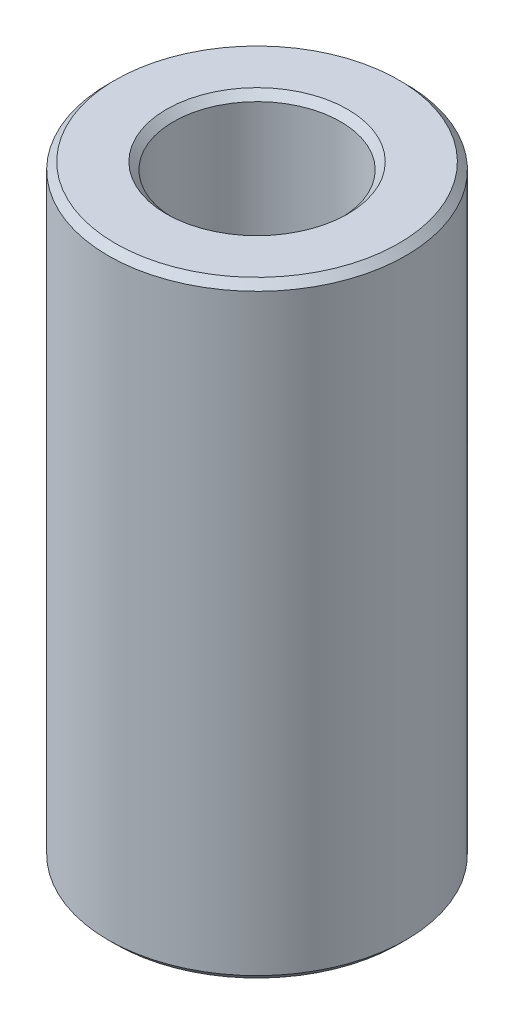
SolidWorks part; units mm, degrees
ref_plane "Front Plane" through (0, 0, 0) normal (0, 0, 1) x (1, 0, 0)
ref_plane "Top Plane" through (0, 0, 0) normal (0, 1, 0) x (1, 0, 0)
ref_plane "Right Plane" through (0, 0, 0) normal (1, 0, 0) x (0, 0, -1)
sketch "Sketch1" plane through (0, 0, 0) normal (0, 1, 0) x (1, 0, 0)
  circle A0 centre (0, 0) radius 40
  dimension "SLEEVE_OD" = 80
extrude "Boss-Extrude1" add sketch "Sketch1" along normal blind 163.158
sketch "Sketch2" plane through (0, 0, 0) normal (0, 1, 0) x (1, 0, 0)
  circle A0 centre (0, 0) radius 22.4699
  dimension "BORE_D" = 44.9398
extrude "Cut-Extrude1" cut sketch "Sketch2" along normal through all
chamfer "Chamfer1" distance 1.9075 angle 45 4 edges at (0, 163.158, 22.4699) (0, 0, 22.4699) (0, 0, 40) (0, 163.158, 40)
